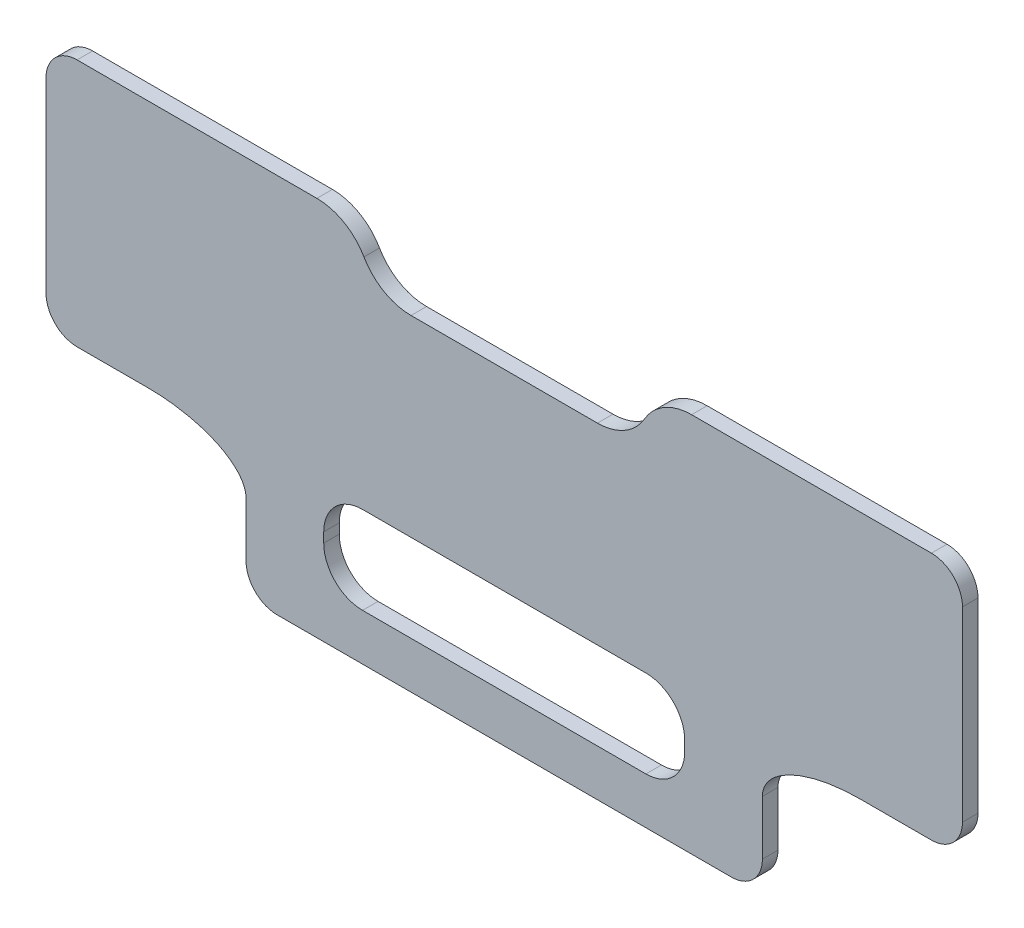
SolidWorks part; units mm, degrees
ref_plane "Front Plane" through (0, 0, 0) normal (0, 0, 1) x (1, 0, 0)
ref_plane "Top Plane" through (0, 0, 0) normal (0, 1, 0) x (1, 0, 0)
ref_plane "Right Plane" through (0, 0, 0) normal (1, 0, 0) x (0, 0, -1)
sketch "Sketch1" plane through (0, 0, 0) normal (0, 0, 1) x (1, 0, 0)
  line L1 (59, 26) -> (-59, 26)
  line L2 (59, 26) -> (59, -26)
  line L3 (59, -26) -> (-59, -26)
  line L4 (-59, 26) -> (-59, -26)
  line L5 (59, 26) -> (-59, -26) construction
  line L6 (59, -26) -> (-59, 26) construction
  point P0 (0, 0)
  dimension "D1" = 118
  dimension "D2" = 52
extrude "Boss-Extrude1" add sketch "Sketch1" along normal blind 2
sketch "Sketch3" plane through (0, 0, 2) normal (0, 0, 1) x (1, 0, 0)
  line L0 (-33.2417, -12) -> (-33.2417, -23) construction
  line L1 (-59, -6) -> (-45.8694, -6) construction
  line L2 (-33.2417, -12) -> (-33.2417, -23)
  line L3 (-59, -6) -> (-45.8694, -6)
  line L8 (-59, 26) -> (-59, -26)
  line L9 (-59, -26) -> (59, -26)
  line L10 (59, -26) -> (59, 26)
  line L11 (59, 26) -> (-59, 26)
  line L12 (-59, 26) -> (-59, -26)
  line L13 (-59, -26) -> (59, -26)
  line L14 (59, -26) -> (59, 26)
  line L15 (59, 26) -> (-59, 26)
  line L20 (59, -6) -> (59, 109)
  line L21 (59, 109) -> (54, 109)
  line L22 (54, 109) -> (54, 0)
  line L23 (50, -4) -> (29.7908, -4)
  line L24 (23.477, -7) -> (23.477, -18)
  line L25 (17.1632, -21) -> (-17.1632, -21)
  line L26 (-23.477, -18) -> (-23.477, -7)
  line L27 (-29.7908, -4) -> (-50, -4)
  line L28 (-54, 0) -> (-54, 109)
  line L29 (-54, 109) -> (-59, 109)
  line L30 (-59, 109) -> (-59, -6)
  line L31 (-59, -6) -> (-45.8694, -6)
  line L32 (-33.2417, -12) -> (-33.2417, -23)
  line L33 (-33.2417, -23) -> (33.2417, -23)
  line L34 (33.2417, -23) -> (33.2417, -12)
  line L35 (45.8694, -6) -> (59, -6)
  line L36 (59, -6) -> (59, 109)
  line L37 (59, 109) -> (54, 109)
  line L38 (54, 109) -> (54, 0)
  line L39 (50, -4) -> (29.7908, -4)
  line L40 (23.477, -7) -> (23.477, -18)
  line L41 (17.1632, -21) -> (-17.1632, -21)
  line L42 (-23.477, -18) -> (-23.477, -7)
  line L43 (-29.7908, -4) -> (-50, -4)
  line L44 (-54, 0) -> (-54, 109)
  line L45 (-54, 109) -> (-59, 109)
  line L46 (-59, 109) -> (-59, -6)
  line L47 (-59, -6) -> (-45.8694, -6)
  line L48 (-33.2417, -12) -> (-33.2417, -23)
  line L49 (-33.2417, -23) -> (33.2417, -23)
  line L50 (33.2417, -23) -> (33.2417, -12)
  line L51 (45.8694, -6) -> (59, -6)
  arc A2 (50, -4) -> (54, 0) centre (50, 0) ccw
  arc A3 (-54, 0) -> (-50, -4) centre (-50, 0) ccw
  arc A4 (50, -4) -> (54, 0) centre (50, 0) ccw
  arc A5 (-54, 0) -> (-50, -4) centre (-50, 0) ccw
  ellipse E0 centre (-45.8694, -12) end of major axis (-58.497, -12) minor radius 6 (-33.2417, -12) -> (-45.8694, -6) ccw construction
  ellipse E1 centre (-45.8694, -12) end of major axis (-58.497, -12) minor radius 6 (-33.2417, -12) -> (-45.8694, -6) ccw
  ellipse E8 centre (29.7908, -7) end of major axis (23.477, -7) minor radius 3 (29.7908, -4) -> (23.477, -7) ccw
  ellipse E9 centre (17.1632, -18) end of major axis (23.477, -18) minor radius 3 (17.1632, -21) -> (23.477, -18) ccw
  ellipse E10 centre (-17.1632, -18) end of major axis (-23.477, -18) minor radius 3 (-23.477, -18) -> (-17.1632, -21) ccw
  ellipse E11 centre (-29.7908, -7) end of major axis (-23.477, -7) minor radius 3 (-23.477, -7) -> (-29.7908, -4) ccw
  ellipse E12 centre (-45.8694, -12) end of major axis (-58.497, -12) minor radius 6 (-33.2417, -12) -> (-45.8694, -6) ccw
  ellipse E13 centre (45.8694, -12) end of major axis (58.497, -12) minor radius 6 (45.8694, -6) -> (33.2417, -12) ccw
  ellipse E14 centre (29.7908, -7) end of major axis (23.477, -7) minor radius 3 (29.7908, -4) -> (23.477, -7) ccw
  ellipse E15 centre (17.1632, -18) end of major axis (23.477, -18) minor radius 3 (17.1632, -21) -> (23.477, -18) ccw
  ellipse E16 centre (-17.1632, -18) end of major axis (-23.477, -18) minor radius 3 (-23.477, -18) -> (-17.1632, -21) ccw
  ellipse E17 centre (-29.7908, -7) end of major axis (-23.477, -7) minor radius 3 (-23.477, -7) -> (-29.7908, -4) ccw
  ellipse E18 centre (-45.8694, -12) end of major axis (-58.497, -12) minor radius 6 (-33.2417, -12) -> (-45.8694, -6) ccw
  ellipse E19 centre (45.8694, -12) end of major axis (58.497, -12) minor radius 6 (45.8694, -6) -> (33.2417, -12) ccw
  line M29 (-59, 26) -> (-59, -26)
  line M30 (-59, -26) -> (59, -26)
  line M31 (59, -26) -> (59, 26)
  dimension "D1" = 0
  dimension "D2" = 0
extrude "Cut-Extrude1" cut sketch "Sketch3" against normal blind 10 contours L51 E19 L50 L49 L2 E1 L3 M29 M30 M31 region at (-34.4386, -17.5, 2)
sketch "Sketch4" plane through (0, 0, 2) normal (0, 0, 1) x (1, 0, 0)
  line L0 (59, 26) -> (-59, 26) construction
  line L1 (-19, 26) -> (19, 26)
  line L2 (-19, 26) -> (-19, 19)
  line L3 (-19, 19) -> (19, 19)
  line L4 (19, 26) -> (19, 19)
  line L5 (59, -6) -> (59, 26) construction
  line L10 (-59, 26) -> (-59, -6) construction
  dimension "D1" = 7
  dimension "D2" = 40
  dimension "D3" = 40
extrude "Cut-Extrude2" cut sketch "Sketch4" against normal blind 10
sketch "Sketch5" plane through (0, 0, 2) normal (0, 0, 1) x (1, 0, 0)
  line L0 (-33.2417, -12) -> (-33.2417, -23) construction
  line L1 (-23.2417, -17) -> (23.2417, -17)
  line L2 (-23.2417, -17) -> (-23.2417, -5.7473)
  line L3 (-23.2417, -5.7473) -> (23.2417, -5.7473)
  line L4 (23.2417, -17) -> (23.2417, -5.7473)
  line L5 (33.2417, -23) -> (33.2417, -12) construction
  line L6 (-33.2417, -23) -> (33.2417, -23) construction
  dimension "D1" = 10
  dimension "D2" = 10
  dimension "D3" = 6
extrude "Cut-Extrude3" cut sketch "Sketch5" against normal blind 10
fillet "Fillet1" radius 5 4 edges at (23.2417, -17, 1) (23.2417, -5.7473, 1) (-23.2417, -17, 1) (-23.2417, -5.7473, 1)
fillet "Fillet2" radius 7 2 edges at (19, 19, 1) (-19, 19, 1)
fillet "Fillet3" radius 7 2 edges at (-19, 26, 1) (19, 26, 1)
fillet "Fillet4" radius 4 4 edges at (33.2417, -23, 1) (-33.2417, -23, 1) (-59, -6, 1) (59, -6, 1)
fillet "Fillet5" radius 4 2 edges at (-59, 26, 1) (59, 26, 1)
